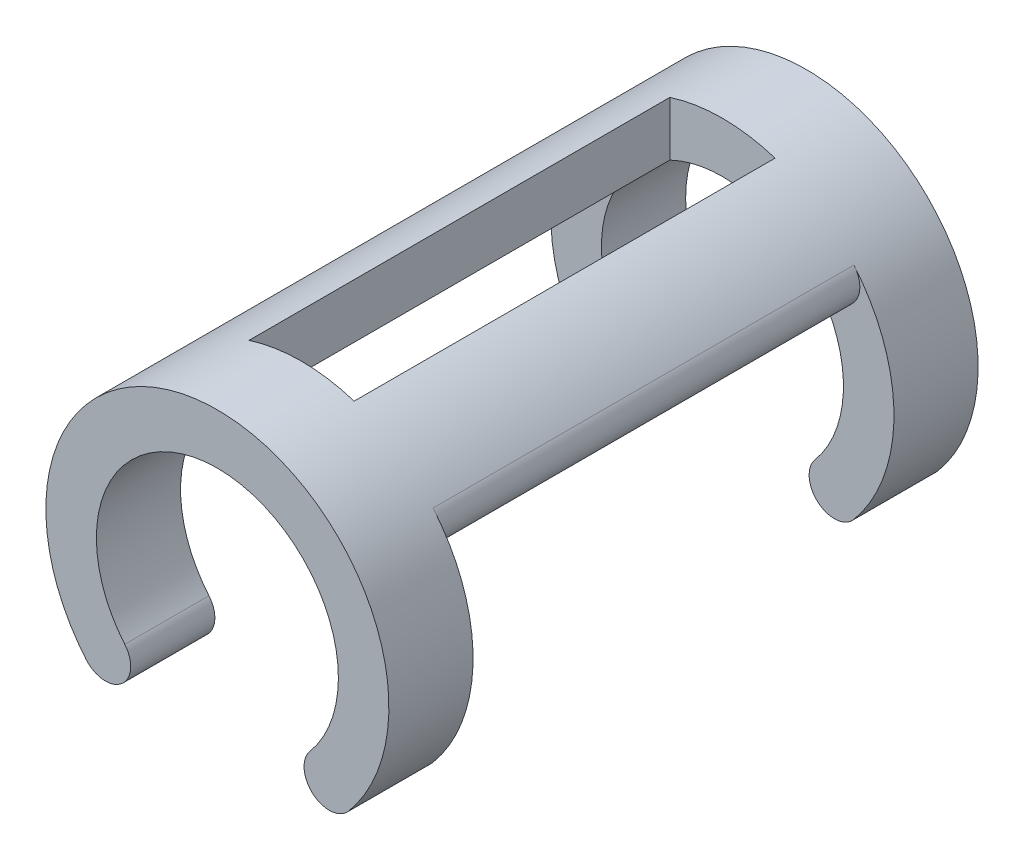
SolidWorks part; units mm, degrees
ref_plane "Front Plane" through (0, 0, 0) normal (0, 0, 1) x (1, 0, 0)
ref_plane "Top Plane" through (0, 0, 0) normal (0, 1, 0) x (1, 0, 0)
ref_plane "Right Plane" through (0, 0, 0) normal (1, 0, 0) x (0, 0, -1)
sketch "Sketch1" plane through (0, 0, 0) normal (0, 0, 1) x (1, 0, 0)
  circle A0 centre (0, 0) radius 4.075
  circle A1 centre (0, 0) radius 2.875
  dimension "D1" = 5.75
  dimension "D2" = 1.2
extrude "Boss-Extrude1" add sketch "Sketch1" along normal mid plane 14
sketch "Sketch4" plane through (0, 0, 0) normal (0, 0, -1) x (-1, 0, 0)
  line L0 (-3.5291, 2.0375) -> (0, 0)
  line L1 (0, 0) -> (3.5291, 2.0375)
  line L2 (0, 0) -> (0, -4.075) construction
  arc A3 (-3.5291, 2.0375) -> (3.5291, 2.0375) centre (0, 0) ccw
  point P4 (0, -4.075)
  dimension "D1" = 120
extrude "Cut-Extrude2" cut sketch "Sketch4" against normal blind 5 and the other way blind 5
sketch "Sketch5" plane through (0, 0, 0) normal (0, 0, -1) x (-1, 0, 0)
  line L0 (-2.6194, -3.1216) -> (0, 0)
  line L1 (0, 0) -> (2.6194, -3.1216)
  line L2 (0, 0) -> (0, -4.075) construction
  arc A3 (-2.6194, -3.1216) -> (2.6194, -3.1216) centre (0, 0) ccw
  point P4 (0, -4.075)
  dimension "D1" = 40
extrude "Cut-Extrude3" cut sketch "Sketch5" against normal through all both and the other way through all
fillet "Fillet2" radius 0.6 12 edges at (-3.5291, 2.0375, 0) (-2.4898, 1.4375, 0) (3.5291, 2.0375, 0) (2.4898, 1.4375, 0) (-2.6194, -3.1216, 6) (-1.848, -2.2024, 6) (2.6194, -3.1216, 6) (1.848, -2.2024, 6) (-2.6194, -3.1216, -6) (-1.848, -2.2024, -6) (1.848, -2.2024, -6) (2.6194, -3.1216, -6)
sketch "Sketch6" plane through (0, 0, 0) normal (0, 1, 0) x (1, 0, 0)
  line L0 (4.075, 7) -> (-4.075, 7) construction
  line L1 (-1.25, 5) -> (1.25, 5)
  line L2 (-1.25, 5) -> (-1.25, -5)
  line L3 (-1.25, -5) -> (1.25, -5)
  line L4 (1.25, 5) -> (1.25, -5)
  point P6 (0, 7)
  point P7 (0, 5)
  point P9 (-1.25, 0)
  dimension "D1" = 2.5
  dimension "D2" = 10
extrude "Cut-Extrude4" cut sketch "Sketch6" along normal through all both and the other way through all
